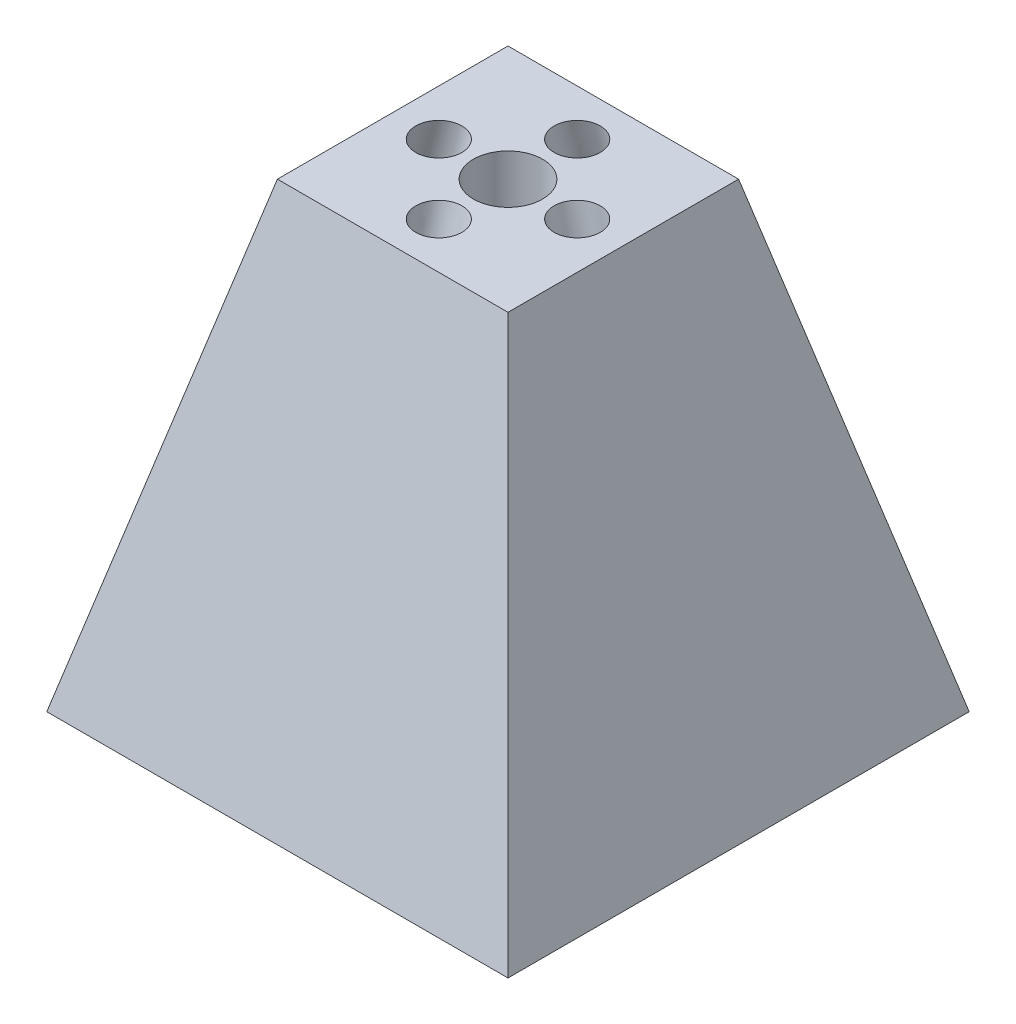
SolidWorks part; units mm, degrees
ref_plane "Front Plane" through (0, 0, 0) normal (0, 0, 1) x (1, 0, 0)
ref_plane "Top Plane" through (0, 0, 0) normal (0, 1, 0) x (1, 0, 0)
ref_plane "Right Plane" through (0, 0, 0) normal (1, 0, 0) x (0, 0, -1)
sketch "Sketch1" plane through (0, 0, 0) normal (0, 1, 0) x (1, 0, 0)
  line L1 (-50, 50) -> (50, 50)
  line L2 (-50, 50) -> (-50, -50)
  line L3 (-50, -50) -> (50, -50)
  line L4 (50, 50) -> (50, -50)
  line L5 (-50, 50) -> (50, -50) construction
  line L6 (-50, -50) -> (50, 50) construction
  point P0 (0, 0)
  dimension "D1" = 100
ref_plane "Plane1" through (0, 100, 0) normal (0, 1, 0) x (1, 0, 0)
sketch "Sketch2" plane through (0, 100, 0) normal (0, 1, 0) x (1, 0, 0)
  line L0 (-50, 50) -> (50, -50) construction
  line L1 (-25, 25) -> (25, 25)
  line L2 (-25, 25) -> (-25, -25)
  line L3 (-25, -25) -> (25, -25)
  line L4 (25, 25) -> (25, -25)
  line L5 (-25, 25) -> (25, -25) construction
  line L6 (-25, -25) -> (25, 25) construction
  point P0 (0, 0)
  dimension "D1" = 50
loft "Loft1" add profiles "Sketch2", "Sketch1" connector at (25, 100, -25) connector at (50, 0, -50)
sketch "Sketch3" plane through (0, 100, 0) normal (0, 1, 0) x (1, 0, 0)
  circle A0 centre (0, 0) radius 7.5
  dimension "D1" = 15
extrude "Cut-Extrude1" cut sketch "Sketch3" against normal through all
sketch "Sketch4" plane through (0, 100, 0) normal (0, 1, 0) x (1, 0, 0)
  circle A0 centre (0, 15) radius 5
  circle A1 centre (15, 0) radius 5
  circle A2 centre (0, -15) radius 5
  circle A3 centre (-15, 0) radius 5
  point P2 (0, 0)
  point P4 (0, 0)
  point P12 (0, 0)
  dimension "D1" = 10
  dimension "D2" = 15
  dimension "D4" = 15
  dimension "D3" = 4
sketch "Sketch5" plane through (0, 0, 0) normal (0, -1, 0) x (1, 0, 0)
  line L0 (-50, 50) -> (50, 50) construction
  line L1 (-50, -50) -> (-50, 50) construction
  circle A0 centre (0, 40) radius 5
  circle A1 centre (40, 0) radius 5
  circle A2 centre (0, -40) radius 5
  circle A3 centre (-40, 0) radius 5
  point P14 (0, 0)
  dimension "D1" = 10
  dimension "D2" = 10
  dimension "D4" = 10
  dimension "D3" = 4
sketch "Sketch6" plane through (0, 0, 0) normal (0, 0, 1) x (1, 0, 0)
  line L0 (-15, 100) -> (-40, 0) construction
  line L1 (15, 100) -> (40, 0) construction
sketch "Sketch7" plane through (0, 0, 0) normal (1, 0, 0) x (0, 0, -1)
  line L0 (-15, 100) -> (-40, 0) construction
  line L1 (15, 100) -> (40, 0) construction
loft "Cut-Loft1" cut section "Sketch4" section "Sketch5" connector at (4.2779, 100, 12.4117) connector at (0.8349, 0, 35.0702)
loft "Cut-Loft2" cut section "Sketch4<4>" section "Sketch5<4>" connector at (18.2711, 100, -3.7816) connector at (40.3234, 0, -4.9895)
sketch "Sketch4<4>" plane through (0, 100, 0) normal (0, 1, 0) x (1, 0, 0) same geometry as "Sketch4"
sketch "Sketch5<4>" plane through (0, 0, 0) normal (0, -1, 0) x (1, 0, 0) same geometry as "Sketch5"
loft "Cut-Loft3" cut section "Sketch4<5>" section "Sketch5<5>" connector at (4.9893, 100, -14.6735) connector at (2.6499, 0, -35.7599)
sketch "Sketch4<5>" plane through (0, 100, 0) normal (0, 1, 0) x (1, 0, 0) same geometry as "Sketch4"
sketch "Sketch5<5>" plane through (0, 0, 0) normal (0, -1, 0) x (1, 0, 0) same geometry as "Sketch5"
loft "Cut-Loft4" cut section "Sketch5<6>" section "Sketch4<6>" connector at (-35.821, 0, 2.7451) connector at (-11.5272, 100, 3.5972)
sketch "Sketch5<6>" plane through (0, 0, 0) normal (0, -1, 0) x (1, 0, 0) same geometry as "Sketch5"
sketch "Sketch4<6>" plane through (0, 100, 0) normal (0, 1, 0) x (1, 0, 0) same geometry as "Sketch4"
